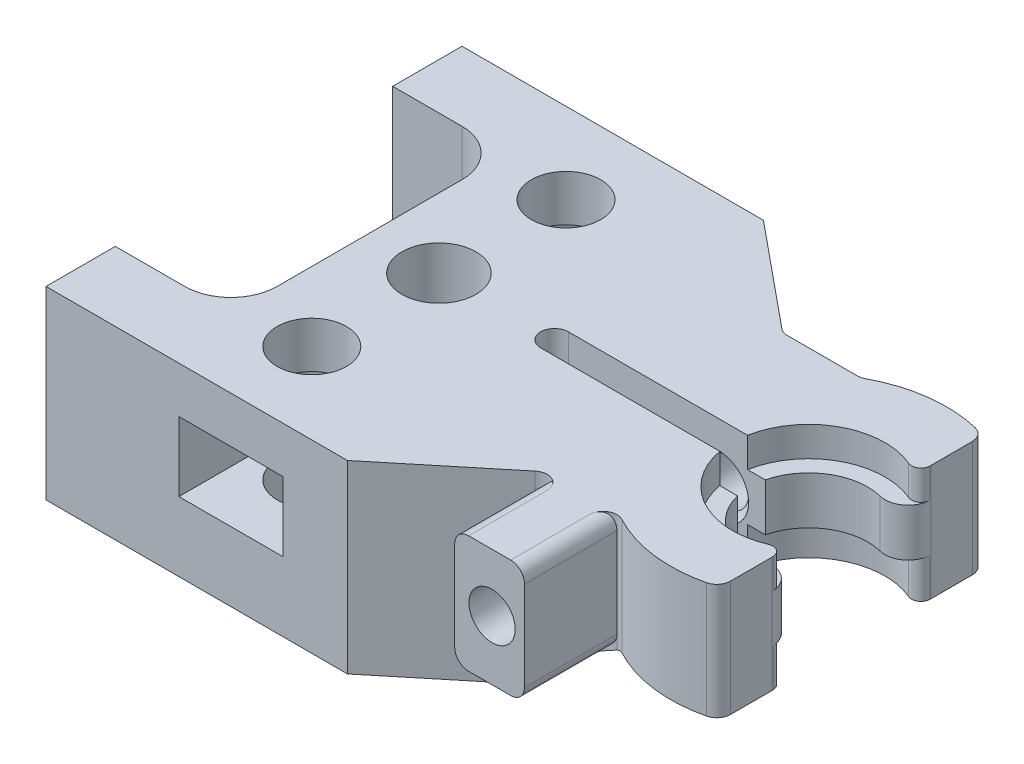
SolidWorks part; units mm, degrees
ref_plane "Front Plane" through (0, 0, 0) normal (0, 0, 1) x (1, 0, 0)
ref_plane "Top Plane" through (0, 0, 0) normal (0, 1, 0) x (1, 0, 0)
ref_plane "Right Plane" through (0, 0, 0) normal (1, 0, 0) x (0, 0, -1)
sketch "Sketch1" plane through (0, 0, 0) normal (0, 0, 1) x (1, 0, 0)
  line L0 (-3.3, 35) -> (-3.3, 33.7126)
  line L1 (-3.3, 33.7126) -> (-2.55, 33.7126)
  line L2 (-2.55, 33.7126) -> (-2.55, 31.6528)
  line L3 (-2.55, 31.6528) -> (-3.3, 31.6528)
  line L4 (-3.3, 31.6528) -> (-3.3, 30)
  line L5 (-3.3, 30) -> (-5.975, 30)
  line L6 (-5.975, 30) -> (-5.975, 35)
  line L7 (-5.975, 35) -> (-3.3, 35)
  line L8 (0, 0) -> (0, 43.3729) construction
  point P11 (-4.6375, 35)
  point P12 (-3.3, 30.8264)
  point P13 (-2.55, 32.6827)
  dimension "D1" = 5
  dimension "D2" = 30
  dimension "D3" = 3.3
  dimension "D4" = 3.3
  dimension "D5" = 2.55
revolve "Revolve1" add sketch "Sketch1" angle 360 about L8
sketch "Sketch2" plane through (0, 35, 0) normal (0, 1, 0) x (1, 0, 0)
  line L0 (-19, 9) -> (-10.9585, 9)
  line L1 (-19, -9) -> (-10.9585, -9)
  line L2 (-19, -9) -> (-19, 9)
  line L3 (0, 0) -> (-10.9585, 9)
  line L4 (0, 0) -> (-10.9585, -9)
  line L6 (-19, 9) -> (-24, 9)
  line L7 (-19, 9) -> (-19, 6)
  line L8 (-19, 6) -> (-24, 6)
  line L9 (-24, 9) -> (-24, 6)
  line L10 (-19, -9) -> (-24, -9)
  line L11 (-19, -9) -> (-19, -6)
  line L12 (-19, -6) -> (-24, -6)
  line L13 (-24, -9) -> (-24, -6)
  line L14 (-8.9905, 5.2) -> (-0.8022, 5.2)
  line L15 (-8.9905, 5.2) -> (-8.9905, -5.2)
  line L16 (-8.9905, -5.2) -> (-0.8022, -5.2)
  line L17 (-0.8022, 5.2) -> (-0.8022, -5.2)
  circle A0 centre (-16, 0) radius 1.6
  circle A1 centre (-16, 5.5) radius 1.5
  circle A2 centre (-16, -5.5) radius 1.5
  circle A3 centre (0, 0) radius 4.3057
  circle M1 centre (0, 0) radius 5.975
  dimension "D2" = 3.2
  dimension "D5" = 3
  dimension "D6" = 3
  dimension "D1" = 16
  dimension "D3" = 5.5
  dimension "D4" = 5.5
  dimension "D7" = 3
  dimension "D8" = 9
  dimension "D9" = 9
  dimension "D10" = 24
  dimension "D11" = 3
  dimension "D12" = 3
  dimension "D13" = 5.2
  dimension "D14" = 5.2
extrude "Boss-Extrude1" add sketch "Sketch2" against normal blind 8 contours L6 L9 L8 L2 | L13 L10 L2 L12 | L16 L15 L14 L3 L0 L2 L1 L4 A2 A1 A0 | L15 L16 L4 L3 L14 M1 | L14 L3 M1 | L4 L16 M1 region at (-13.5916, 35, 0) region at (-21.5, 35, -7.5) region at (-4.685, 35, -4.7441) region at (-7.232, 35, 0) region at (-21.5, 35, 7.5) region at (-4.685, 35, 4.7441)
sketch "Sketch3" plane through (0, 0, 0) normal (0, 1, 0) x (1, 0, 0)
  line L1 (10.087, 10.1783) -> (1.85, 10.1783)
  line L2 (10.087, 10.1783) -> (10.087, -10.4323)
  line L3 (10.087, -10.4323) -> (1.85, -10.4323)
  line L4 (1.85, 10.1783) -> (1.85, -10.4323)
  dimension "D1" = 1.85
extrude "Cut-Extrude1" cut sketch "Sketch3" along normal through all
chamfer "Chamfer1" distance 3 angle 45 1 edges at (-5.975, 27, 0)
fillet "Fillet4" radius 1 2 edges at (1.85, 32.6827, -1.755) (1.85, 32.6827, 1.755)
fillet "Fillet5" radius 0.4 4 edges at (1.6558, 34.3563, -2.8545) (1.6558, 30.8264, -2.8545) (1.6558, 30.8264, 2.8545) (1.6558, 34.3563, 2.8545)
fillet "Fillet6" radius 2 2 edges at (-19, 31, 6) (-19, 31, -6)
sketch "Sketch5" plane through (0, 0, 0) normal (0, 1, 0) x (1, 0, 0)
  line L0 (0, 0) -> (-11, 0) construction
  line L1 (0, -0.6) -> (-11, -0.6)
  line L2 (0, 0.6) -> (-11, 0.6)
  arc A0 (0, -0.6) -> (0, 0.6) centre (0, 0) ccw
  arc A1 (-11, 0.6) -> (-11, -0.6) centre (-11, 0) ccw
  point P3 (-5.5, 0)
  dimension "D1" = 11
extrude "Cut-Extrude2" cut sketch "Sketch5" along normal through all
sketch "Sketch6" plane through (0, 35, 0) normal (0, 1, 0) x (1, 0, 0)
  line L0 (-16, -5.5) -> (-16, -11.8493) construction
  line L1 (-13.75, -5.5) -> (-13.75, -11.8493)
  line L2 (-18.25, -5.5) -> (-18.25, -11.8493)
  line L3 (-16, 5.5) -> (-16, 11.8132) construction
  line L4 (-18.25, 5.5) -> (-18.25, 11.8132)
  line L5 (-13.75, 5.5) -> (-13.75, 11.8132)
  arc A0 (-13.75, -5.5) -> (-18.25, -5.5) centre (-16, -5.5) ccw
  arc A1 (-18.25, -11.8493) -> (-13.75, -11.8493) centre (-16, -11.8493) ccw
  arc A2 (-18.25, 5.5) -> (-13.75, 5.5) centre (-16, 5.5) ccw
  arc A3 (-13.75, 11.8132) -> (-18.25, 11.8132) centre (-16, 11.8132) ccw
  point P3 (-16, -8.6747)
  point P8 (-16, 8.6566)
extrude "Cut-Extrude3" cut sketch "Sketch6" against normal blind 3 from offset 2 offset against normal yes
sketch "Sketch7" plane through (0, 27, 0) normal (0, -1, 0) x (1, 0, 0)
  circle A0 centre (-16, 0) radius 1.6
  circle A1 centre (-16, 0) radius 2.5
extrude "Boss-Extrude2" add sketch "Sketch7" along normal blind 0.5
chamfer "Chamfer2" distance 0.5 angle 45 1 edges at (-16, 27, 2.5)
sketch "Sketch8" plane through (0, 0, 0) normal (0, 0, 1) x (1, 0, 0)
  line L0 (0, 35) -> (-10.9585, 35) construction
  circle A0 centre (-4.5, 32.5) radius 1
  dimension "D3" = 2
  dimension "D1" = 4.5
  dimension "D2" = 2.5
extrude "Cut-Extrude4" cut sketch "Sketch8" against normal through all and the other way through all
fillet "Fillet7" radius 0.6 6 edges at (1.85, 32.5, -5.6814) (1.85, 32.5, 5.6814) (-2.9429, 32.5, -5.2) (-6.3316, 31.3909, -5.2) (-2.9429, 32.5, 5.2) (-6.3316, 31.3909, 5.2)
sketch "Sketch9" plane through (0, 0, 5.2) normal (0, 0, 1) x (1, 0, 0)
  line L1 (-6.1168, 35) -> (-3.0969, 35)
  line L2 (-6.1168, 35) -> (-6.1168, 29.9227)
  line L3 (-6.1168, 29.9227) -> (-3.0969, 29.9227)
  line L4 (-3.0969, 35) -> (-3.0969, 29.9227)
  circle A0 centre (-4.5, 32.5) radius 1 construction
  circle A1 centre (-4.5, 32.5) radius 1
extrude "Boss-Extrude3" add sketch "Sketch9" along normal blind 4
fillet "Fillet8" radius 0.6 4 edges at (-6.1168, 29.9227, 7.2) (-3.0969, 29.9227, 7.2) (-3.0969, 35, 7.2) (-6.1168, 35, 7.2)
chamfer "Chamfer3" distance 0.3 angle 45 2 edges at (-3.5, 32.5, -0.6) (-5.5, 32.5, 0.6)
